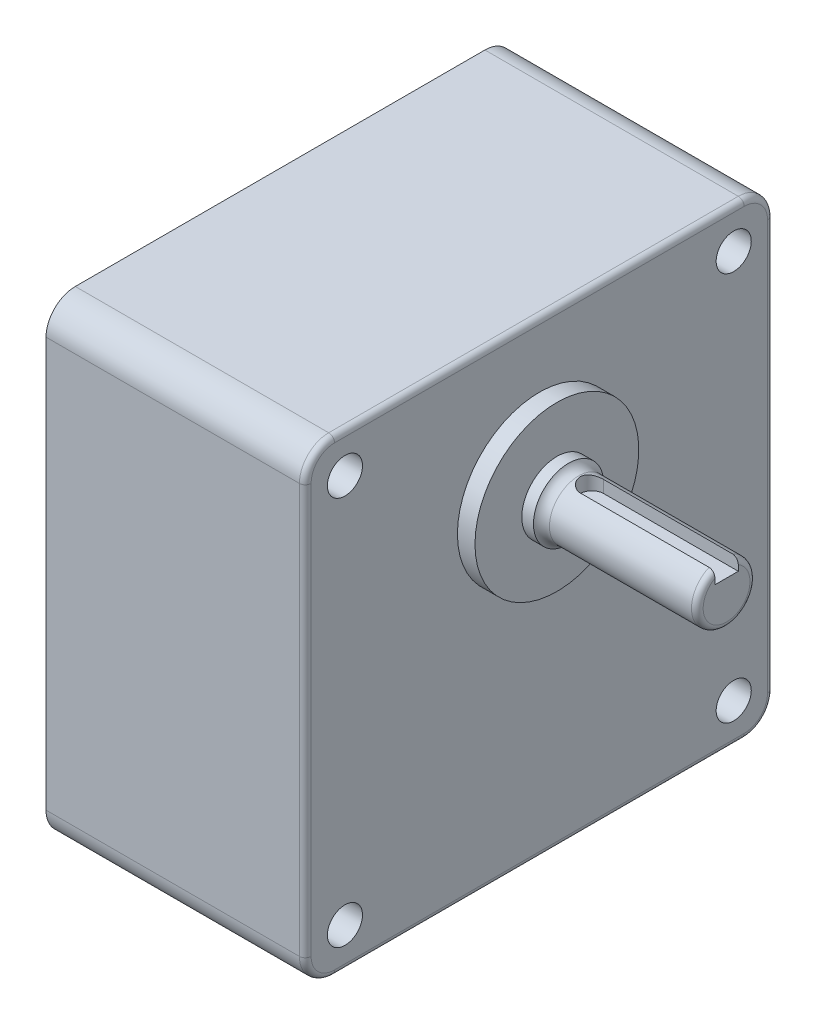
SolidWorks part; units mm, degrees
ref_plane "Front Plane" through (0, 0, 0) normal (0, 0, 1) x (1, 0, 0)
ref_plane "Top Plane" through (0, 0, 0) normal (0, 1, 0) x (1, 0, 0)
ref_plane "Right Plane" through (0, 0, 0) normal (1, 0, 0) x (0, 0, -1)
ref_plane "Plane1" through (-5, 0, 0) normal (1, 0, 0) x (0, 0, -1)
sketch "Sketch1" plane through (-5, 0, 0) normal (1, 0, 0) x (0, 0, -1)
  line L0 (0, 25) -> (0, -55) construction
  line L1 (-40, 25) -> (40, 25)
  line L2 (-40, 25) -> (-40, -55)
  line L3 (-40, -55) -> (40, -55)
  line L4 (40, 25) -> (40, -55)
  line L5 (-40, -15) -> (40, -15) construction
  point P10 (0, -15)
  dimension "FIX_2" = 80
  dimension "FIX_3" = 15
extrude "Boss-Extrude1" add sketch "Sketch1" against normal blind 44.3
sketch "Sketch2" plane through (-5, 0, 0) normal (1, 0, 0) x (0, 0, -1)
  line L1 (0, 25) -> (0, -55) construction
  circle A0 centre (0, -15) radius 47 construction
  circle A1 centre (-33.218, 18.25) radius 3
  circle A2 centre (33.218, 18.25) radius 3
  circle A3 centre (33.218, -48.25) radius 3
  circle A4 centre (-33.218, -48.25) radius 3
  dimension "FIX_5" = 94
  dimension "FIX_6" = 6
  dimension "FIX_7" = 66.5
extrude "Cut-Extrude1" cut sketch "Sketch2" against normal through all
fillet "Fillet1" radius 5 4 edges at (-27.15, -55, -40) (-27.15, -55, 40) (-27.15, 25, 40) (-27.15, 25, -40)
fillet "Fillet2" radius 1 8 edges at (-5, 23.5355, -38.5355) (-5, -15, -40) (-5, -53.5355, -38.5355) (-5, -55, 0) (-5, -53.5355, 38.5355) (-5, -15, 40) (-5, 23.5355, 38.5355) (-5, 25, 0)
sketch "Sketch3" plane through (0, 0, 0) normal (0, 0, 1) x (1, 0, 0)
  line L0 (-5, 0) -> (27, 0) construction
  line L1 (-5, 25) -> (-5, -55) construction
  line L2 (-5, 14) -> (-2, 14)
  line L3 (-2, 14) -> (-2, 6)
  line L4 (1.7321, 5) -> (27, 5)
  line L5 (27, 5) -> (27, 0)
  line L7 (-5, 0) -> (-5, 14)
  line L8 (-2, 6) -> (0, 6)
  line L10 (-5, 0) -> (27, 0)
  arc A0 (0, 6) -> (1.7321, 5) centre (1.7321, 7) ccw
  dimension "FIX_15" = 2
  dimension "FIX_10" = 28
  dimension "FIX_11" = 10
  dimension "FIX_12" = 12
  dimension "FIX_13" = 32
  dimension "FIX_14" = 3
  dimension "FIX_16" = 2
revolve "Revolve1" add sketch "Sketch3" angle 360 about L0
fillet "Fillet3" radius 1 1 edges at (27, 0, 5)
ref_plane "Plane2" through (27, 0, 0) normal (1, 0, 0) x (0, 0, -1)
sketch "Sketch4" plane through (27, 0, 0) normal (1, 0, 0) x (0, 0, -1)
  line L0 (2, 4.5826) -> (2, 2.5)
  line L1 (2, 2.5) -> (-2, 2.5)
  line L2 (-2, 2.5) -> (-2, 4.5826)
  arc A0 (2, 4.5826) -> (-2, 4.5826) centre (0, 0) ccw
  point P6 (0, 2.5)
  dimension "FIX_19" = 4
  dimension "FIX_20" = 2.5
extrude "Cut-Extrude2" cut sketch "Sketch4" against normal blind 25
fillet "Fillet4" 2 edges at (2, 3.5413, -2) (2, 3.5413, 2) type full round first side face at (16.8433, 3.5712, -2) second side face at (16.8191, 3.5947, 2) middle face at (2, 3.6456, 0)
sketch "Sketch5" plane through (0, 0, 0) normal (0, 0, 1) x (1, 0, 0)
  line L0 (-46.3, -15) -> (-49.3, -15) construction
  line L1 (-46.3, -15) -> (-46.3, 21.5)
  line L2 (-46.3, 21.5) -> (-49.3, 21.5)
  line L3 (-49.3, 21.5) -> (-49.3, -15)
  line L6 (-46.3, -15) -> (-49.3, -15)
  dimension "FIX_22" = 3
  dimension "FIX_23" = 44.3
  dimension "FIX_24" = 73
revolve "Cut-Revolve1" cut sketch "Sketch5" angle 360 about L0
